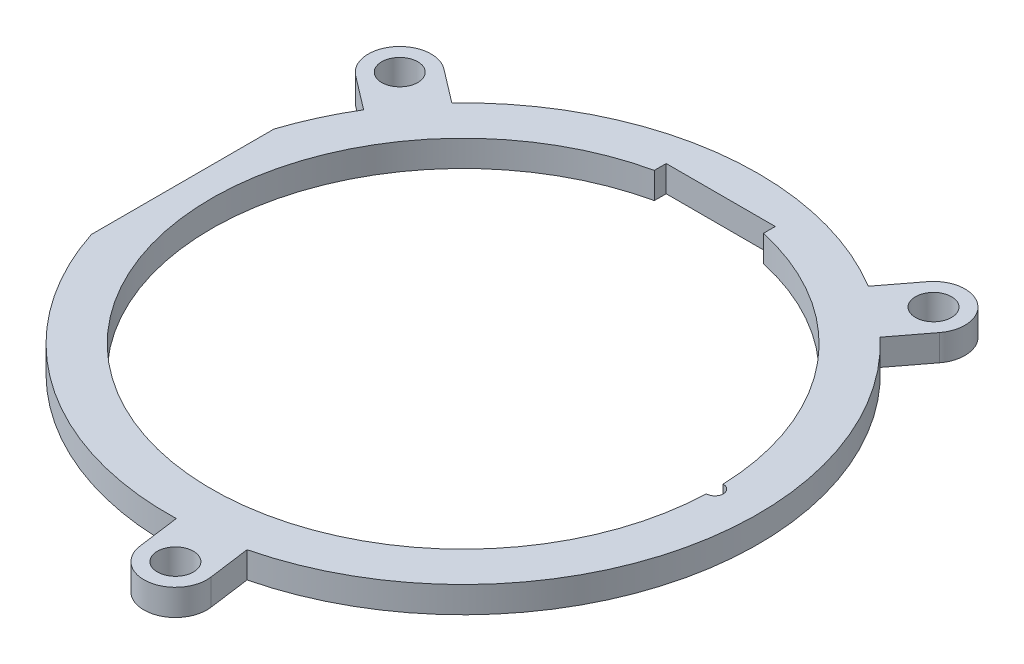
SolidWorks part; units mm, degrees
ref_plane "Front" through (0, 0, 0) normal (0, 0, 1) x (1, 0, 0)
ref_plane "Top" through (0, 0, 0) normal (0, 1, 0) x (1, 0, 0)
ref_plane "Right" through (0, 0, 0) normal (1, 0, 0) x (0, 0, -1)
sketch "Sketch1" plane through (0, 0, 0) normal (0, 1, 0) x (1, 0, 0)
  line L0 (0, -15.24) -> (0, 15.5956) construction
  line L1 (-3.302, 15.5956) -> (3.302, 15.5956)
  line L2 (-3.302, 15.5956) -> (-3.302, 14.878)
  line L3 (3.302, 15.5956) -> (3.302, 14.878)
  circle A0 centre (0, 0) radius 15.24
  circle A1 centre (0, 0) radius 21.59
  dimension "D1" = 30.48
  dimension "D3" = 30.8356
  dimension "D4" = 6.604
  dimension "D2" = 6.35
extrude "Boss-Extrude1" add sketch "Sketch1" along normal mid plane 1.5875 contours A1 A0 L2 L1 L3 region at (-20.9793, 0, 0)
sketch "Sketch2" plane through (0, 0.7937, 0) normal (0, 1, 0) x (1, 0, 0)
  line L0 (0, 18.415) -> (0, -18.415) construction
  line L1 (0, -15.24) -> (0, -21.59) construction
  circle A0 centre (0, 18.415) radius 1.4224
  circle A1 centre (0, -18.415) radius 1.4224
  arc A2 (-3.302, 14.878) -> (3.302, 14.878) centre (0, 0) ccw construction
  circle A3 centre (0, 0) radius 21.59 construction
  dimension "D1" = 2.8448
extrude "Cut-Extrude1" cut sketch "Sketch2" against normal through all
sketch "Sketch3" plane through (0, 0.7937, 0) normal (0, 1, 0) x (1, 0, 0)
  line L0 (-20.8712, 5.5245) -> (-16.9841, 5.5245)
  line L1 (-16.9841, 5.5245) -> (-16.9841, -5.5245)
  line L2 (-16.9841, -5.5245) -> (-20.8712, -5.5245)
  line L3 (-16.9841, -5.5245) -> (-20.8712, -5.5245) construction
  line L4 (-20.8712, 5.5245) -> (-16.9841, 5.5245) construction
  circle A0 centre (0, 0) radius 21.59 construction
  arc A1 (-20.8712, 5.5245) -> (-20.8712, -5.5245) centre (0, 0) ccw
extrude "Cut-Extrude2" cut sketch "Sketch3" against normal through all
sketch "Sketch4" plane through (0, 0.7937, 0) normal (0, 1, 0) x (1, 0, 0)
  line L0 (15.748, 0) -> (-15.24, 0) construction
  circle A0 centre (15.24, 0) radius 0.508
  arc A1 (-3.302, 14.878) -> (3.302, 14.878) centre (0, 0) ccw construction
  dimension "D1" = 30.988
extrude "Cut-Extrude3" cut sketch "Sketch4" against normal through all
sketch "Sketch5" plane through (0, 0.7937, 0) normal (0, 1, 0) x (1, 0, 0)
  line L0 (-12.3201, -16.1591) -> (12.3201, 16.1591) construction
  line L1 (-13.8351, -15.0041) -> (10.8052, 17.3141)
  line L2 (-10.8052, -17.3141) -> (13.8351, 15.0041)
  line L3 (16.1591, -12.3201) -> (-16.1591, 12.3201) construction
  line L4 (15.0041, -13.8351) -> (-17.3141, 10.8052)
  line L5 (17.3141, -10.8052) -> (-15.0041, 13.8351)
  line L6 (0, 0) -> (2.7145, -20.1379) construction
  line L7 (1.8879, 0.2545) -> (4.6025, -19.8834)
  line L8 (-1.8879, -0.2545) -> (0.8266, -20.3924)
  line L9 (-16.1591, 12.3201) -> (12.3201, 16.1591) construction
  circle A0 centre (0, 0) radius 17.86
  arc A1 (-13.8351, -15.0041) -> (-10.8052, -17.3141) centre (-12.3201, -16.1591) ccw
  arc A2 (13.8351, 15.0041) -> (10.8052, 17.3141) centre (12.3201, 16.1591) ccw
  circle A3 centre (12.3201, 16.1591) radius 1.0922
  circle A4 centre (-12.3201, -16.1591) radius 1.0922
  arc A5 (15.0041, -13.8351) -> (17.3141, -10.8052) centre (16.1591, -12.3201) ccw
  arc A6 (-15.0041, 13.8351) -> (-17.3141, 10.8052) centre (-16.1591, 12.3201) ccw
  circle A7 centre (-16.1591, 12.3201) radius 1.0922
  circle A8 centre (16.1591, -12.3201) radius 1.0922
  arc A9 (1.8879, 0.2545) -> (-1.8879, -0.2545) centre (0, 0) ccw
  arc A10 (0.8266, -20.3924) -> (4.6025, -19.8834) centre (2.7145, -20.1379) ccw
  circle A11 centre (2.7145, -20.1379) radius 1.0922
  arc A12 (16.1591, -12.3201) -> (2.7145, -20.1379) centre (0, 0) cw construction
  point P6 (0, 0)
  point P17 (0, 0)
  point P26 (1.3573, -10.0689)
  line M7 (-20.8712, 5.5245) -> (-16.9841, 5.5245)
  line M9 (-16.9841, -5.5245) -> (-20.8712, -5.5245)
  arc M10 (-20.8712, -5.5245) -> (-20.8712, 5.5245) centre (0, 0) ccw
  circle M11 centre (0, -18.415) radius 1.4224
  circle M12 centre (0, 18.415) radius 1.4224
  dimension "D2" = 3.81
  dimension "D1" = 3.81
extrude "Cut-Extrude4" cut sketch "Sketch5" against normal through all contours A6 L5 A0 L1 A2 M12 M10 | A6 A0 L4 M10 M7 | A1 L1 A0 M9 M10 | A5 L4 A0 L2 A1 M11 M10 | A5 A2 L2 A0 L5 M10 | A7 | A3 | A4 | A1 L2 A0 L1 A4 M10 | A11 | A5 L5 A0 L4 A8 M10 | A8 | A10 A5 L4 A0 L7 M10 region at (-16.6582, 0.7937, 10.306) region at (-13.002, 0.7937, 14.0284) region at (-5.4053, 0.7937, 18.8788) region at (-18.0946, 0.7937, -8.0783) region at (-2.5586, 0.7937, -18.0617) region at (9.8123, 0.7937, 16.8747) region at (15.6105, 0.7937, 14.0703) region at (18.0927, 0.7937, -2.4389) region at (12.3201, 0.7937, -16.1591) region at (-12.3201, 0.7937, 16.1591) region at (-16.1591, 0.7937, -12.3201) region at (16.1591, 0.7937, 12.3201) region at (2.7145, 0.7937, 20.1379)
extrude "Boss-Extrude2" add sketch "Sketch5<3>" against normal up to vertex contours A6 M10 | A2 M10 | A0 M11 | A0 M12 | A0 L8 M11 | L8 A0 M11 | A10 M10 region at (-0.2829, 0.7937, 17.4804) region at (2.9174, 0.7937, 21.6425) region at (-17.3665, 0.7937, -13.2407) region at (0, 0.7937, -17.4932) region at (0.7535, 0.7937, 17.5272) region at (0.9598, 0.7937, 18.5708) region at (13.2407, 0.7937, -17.3665) up to point (15.2315, -0.7937, 0.5079)
sketch "Sketch5<3>" plane through (0, 0.7937, 0) normal (0, 1, 0) x (1, 0, 0) same geometry as "Sketch5"
